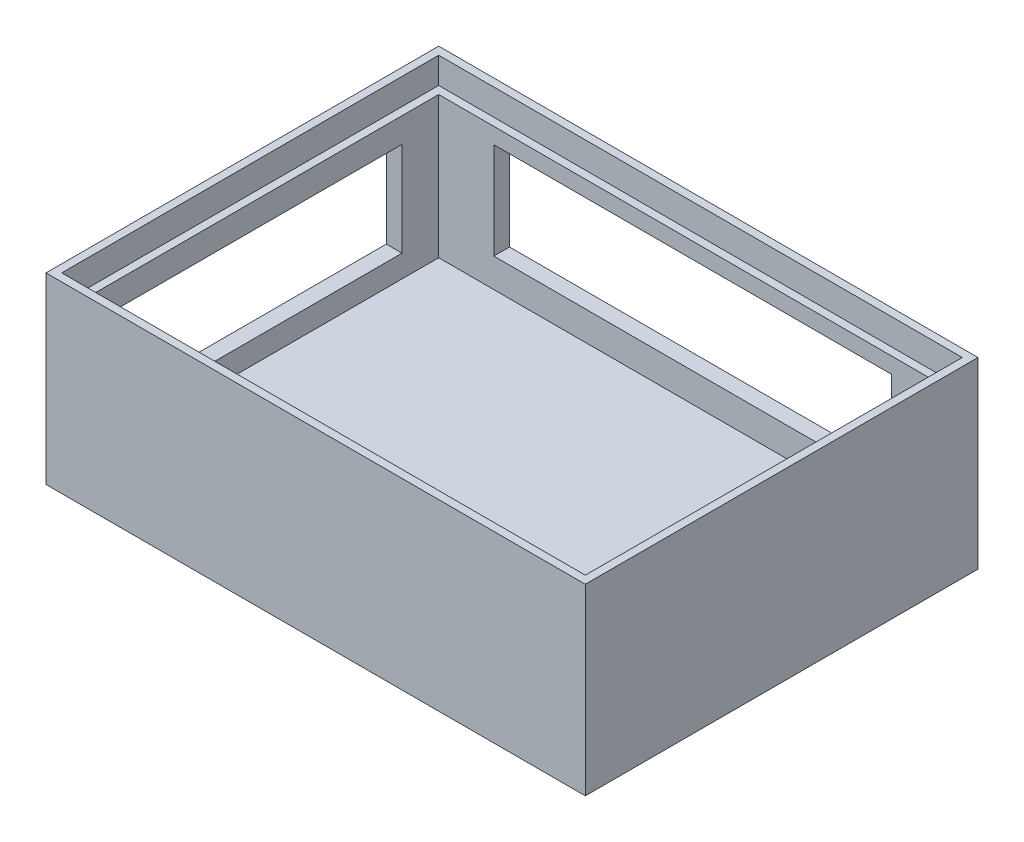
SolidWorks part; units mm, degrees
ref_plane "Plan de face" through (0, 0, 0) normal (0, 0, 1) x (1, 0, 0)
ref_plane "Plan de dessus" through (0, 0, 0) normal (0, 1, 0) x (1, 0, 0)
ref_plane "Plan de droite" through (0, 0, 0) normal (1, 0, 0) x (0, 0, -1)
sketch "Esquisse1" plane through (0, 0, 0) normal (0, 1, 0) x (1, 0, 0)
  line L1 (0, 0) -> (103, 0)
  line L2 (0, 0) -> (0, 75)
  line L3 (0, 75) -> (103, 75)
  line L4 (103, 0) -> (103, 75)
  dimension "D1" = 103
  dimension "D2" = 75
extrude "Boss.-Extru.1" add sketch "Esquisse1" along normal blind 35 contours L3 L4 L1 L2
shell "Coque2" thickness 3 removed face at (51.5, 35, -37.5)
sketch "Esquisse2" plane through (0, 0, 0) normal (0, 1, 0) x (1, 0, 0)
  line L0 (0, 75) -> (103, 75) construction
  line L1 (1.5, 1.5) -> (101.5, 1.5)
  line L2 (1.5, 1.5) -> (1.5, 73.5)
  line L3 (1.5, 73.5) -> (101.5, 73.5)
  line L4 (101.5, 1.5) -> (101.5, 73.5)
  line L5 (103, 0) -> (103, 75) construction
  line L6 (0, 0) -> (103, 0) construction
  line L7 (0, 0) -> (0, 75) construction
  dimension "D1" = 1.5
  dimension "D2" = 1.5
  dimension "D3" = 1.5
  dimension "D4" = 1.5
sketch "Esquisse3" plane through (0, 0, 0) normal (1, 0, 0) x (0, 0, -1)
  line L0 (37.5, 35) -> (37.5, 0) construction
  line L1 (65, 7.2591) -> (10, 7.2591)
  line L2 (65, 7.2591) -> (65, 25.2591)
  line L3 (65, 25.2591) -> (10, 25.2591)
  line L4 (10, 7.2591) -> (10, 25.2591)
  line L5 (0, 35) -> (75, 35) construction
  line L6 (0, 0) -> (75, 0) construction
  point P10 (37.5, 25.2591)
  dimension "D1" = 55
  dimension "D2" = 18
  dimension "D3" = 0
extrude "Enlèv. mat.-Extru.7" cut sketch "Esquisse3" along normal blind 31 contours L3 L4 L1 L2
sketch "Esquisse5" plane through (0, 0, 0) normal (0, 1, 0) x (1, 0, 0)
  line L0 (0, 75) -> (103, 75) construction
  line L5 (51.5, 75) -> (51.5, 0) construction
  line L6 (0, 0) -> (103, 0) construction
  line L7 (103, 37.5) -> (0, 37.5) construction
  line L8 (103, 0) -> (103, 75) construction
  line L9 (0, 0) -> (0, 75) construction
sketch "Esquisse6" plane through (0, 0, 0) normal (0, 1, 0) x (1, 0, 0)
  line L0 (85.6502, 54) -> (85.6502, 17) construction
  line L1 (85.6502, 17) -> (12.6502, 17) construction
  line L2 (12.6502, 17) -> (12.6502, 54) construction
  line L3 (12.6502, 54) -> (85.6502, 54) construction
sketch "Esquisse7" plane through (0, 0, 0) normal (0, 0, 1) x (1, 0, 0)
  line L0 (41.5, 35) -> (41.5, 15) construction
  line L1 (0, 35) -> (103, 35) construction
  line L2 (41.5, 15) -> (61.5, 15) construction
  line L3 (61.5, 15) -> (61.5, 35) construction
  line L4 (61.5, 35) -> (41.5, 35) construction
  point P4 (51.5, 35)
  dimension "D1" = 20
  dimension "D2" = 20
  dimension "D3" = 0
sketch "Esquisse10" plane through (0, 0, -75) normal (0, 0, -1) x (-1, 0, 0)
  line L0 (-103, 35) -> (-103, 0) construction
  line L1 (-89.4824, 8.5422) -> (-13.5176, 8.5422)
  line L2 (-89.4824, 8.5422) -> (-89.4824, 26.9578)
  line L3 (-89.4824, 26.9578) -> (-13.5176, 26.9578)
  line L4 (-13.5176, 8.5422) -> (-13.5176, 26.9578)
  line L5 (0, 35) -> (-103, 35) construction
  point P4 (-51.5, 26.9578)
  point P7 (-13.5176, 17.75)
  dimension "D1" = 51.5
  dimension "D2" = 17.25
extrude "Enlèv. mat.-Extru.9" cut sketch "Esquisse10" against normal blind 10
sketch "Esquisse11" plane through (0, 35, 0) normal (0, 1, 0) x (1, 0, 0)
  line L0 (0, 0) -> (103, 0) construction
  line L1 (101.5, 73.5) -> (1.5, 73.5)
  line L2 (101.5, 73.5) -> (101.5, 1.5)
  line L3 (101.5, 1.5) -> (1.5, 1.5)
  line L4 (1.5, 73.5) -> (1.5, 1.5)
  line L5 (103, 0) -> (103, 75) construction
  line L6 (0, 75) -> (103, 75) construction
  line L7 (0, 0) -> (0, 75) construction
  dimension "D1" = 1.5
  dimension "D2" = 1.5
  dimension "D3" = 1.5
  dimension "D4" = 1.5
extrude "Enlèv. mat.-Extru.12" cut sketch "Esquisse11" against normal blind 5
